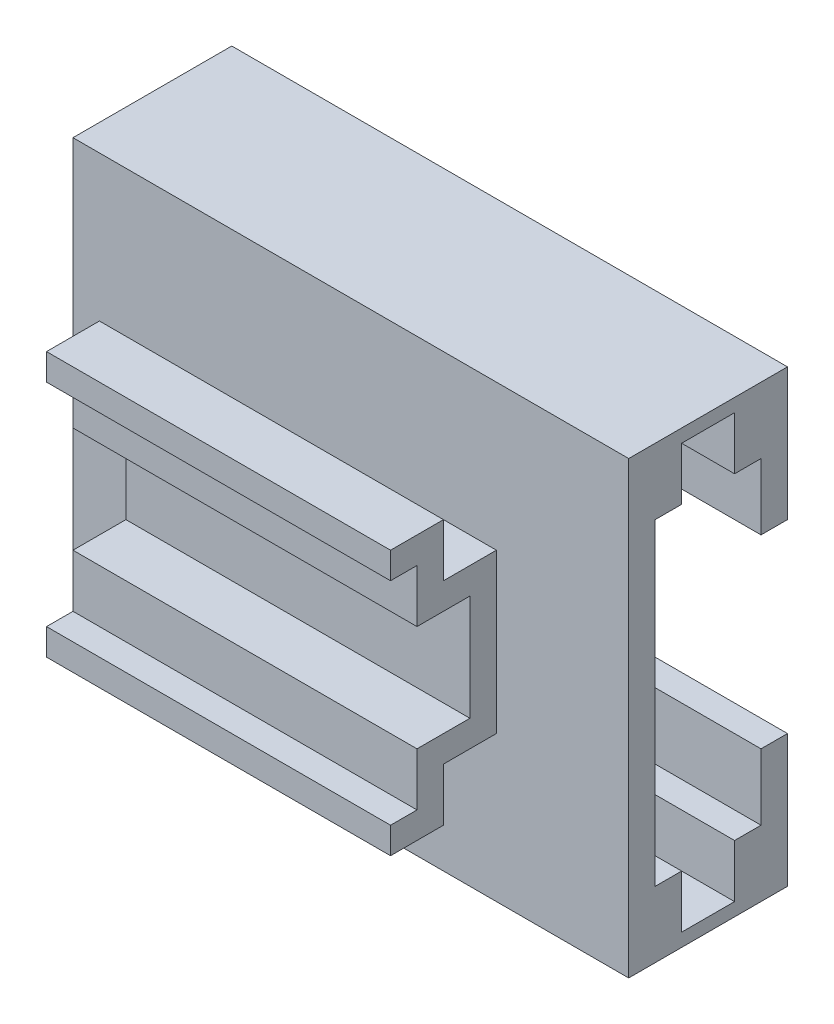
SolidWorks part; units mm, degrees
note: The reader was unsure of these and kept them because the rebuilt part matched: shared geometry of "Esquisse1<3>", "Esquisse1<4>", "Esquisse1<6>".
ref_plane "Plan de face" through (0, 0, 0) normal (0, 0, 1) x (1, 0, 0)
ref_plane "Plan de dessus" through (0, 0, 0) normal (0, 1, 0) x (1, 0, 0)
ref_plane "Plan de droite" through (0, 0, 0) normal (1, 0, 0) x (0, 0, -1)
sketch "Esquisse1" plane through (0, 0, 0) normal (0, 0, 1) x (1, 0, 0)
  line L0 (-10.5, 6) -> (10.5, 6)
  line L1 (10.5, 8.5) -> (-10.5, 8.5)
  line L2 (10.5, 8.5) -> (10.5, -8.5)
  line L3 (10.5, -8.5) -> (-10.5, -8.5)
  line L4 (-10.5, 8.5) -> (-10.5, -8.5)
  line L5 (10.5, 8.5) -> (-10.5, -8.5) construction
  line L6 (10.5, -8.5) -> (-10.5, 8.5) construction
  line L7 (-10.5, -6) -> (10.5, -6)
  line L8 (-9, -8) -> (10.5, -8)
  line L9 (-9, -8) -> (-9, -6)
  line L10 (-12.4007, 0) -> (12.7242, 0) construction
  line L12 (-9, 8) -> (10.5, 8)
  line L13 (10.5, 3.5) -> (-1, 3.5)
  line L14 (-1, 3.5) -> (-1, -3.5)
  line L15 (10.5, -3.5) -> (-1, -3.5)
  line L16 (-9, 8) -> (-9, 6)
  point P0 (0, 0)
  dimension "D1" = 17
  dimension "D2" = 21
  dimension "D3" = 2.5
  dimension "D4" = 2
  dimension "D5" = 2.5
  dimension "D6" = 1.5
  dimension "D7" = 2
  dimension "D8" = 3.5
  dimension "D9" = 1
extrude "Boss.-Extru.1" add sketch "Esquisse1" along normal blind 1 contours L4 L3 L2 L1
extrude "Boss.-Extru.2" add sketch "Esquisse1<3>" against normal blind 1 from offset 4 separate body contours L15 L2 L13 L14 offset against normal yes
sketch "Esquisse1<3>" plane through (0, 0, 0) normal (0, 0, 1) x (1, 0, 0) same geometry as "Esquisse1"
extrude "Boss.-Extru.3" add sketch "Esquisse1<4>" against normal blind 4
sketch "Esquisse1<4>" plane through (0, 0, 0) normal (0, 0, 1) x (1, 0, 0) same geometry as "Esquisse1"
extrude "Enlèv. mat.-Extru.1" cut sketch "Esquisse1<6>" against normal blind 2 from offset 1 contours L9 L8 L2 L7 | L12 L16 L0 L2 offset against normal yes
sketch "Esquisse1<6>" plane through (0, 0, 0) normal (0, 0, 1) x (1, 0, 0) same geometry as "Esquisse1"
sketch "Esquisse2" plane through (-10.5, 0, 0) normal (-1, 0, 0) x (0, 0, 1)
  line L0 (-1.889, 0) -> (9.1913, 0) construction
  line L1 (1, 3) -> (3, 3)
  line L2 (1, 8.5) -> (1, -8.5) construction
  line L3 (3, 3) -> (3, 5)
  line L4 (3, 5) -> (5, 5)
  line L5 (5, 5) -> (5, 4)
  line L6 (3, -3) -> (3, -5)
  line L7 (1, -3) -> (3, -3)
  line L8 (3, -5) -> (5, -5)
  line L9 (1, 3) -> (1, -3)
  line L10 (2, 2) -> (2, -2)
  line L11 (2, -2) -> (4, -2)
  line L12 (4, -2) -> (4, -4)
  line L13 (4, -4) -> (4, -4)
  line L15 (4, 4) -> (4, 4)
  line L16 (4, 2) -> (4, 4)
  line L17 (2, 2) -> (4, 2)
  line L18 (4, -4) -> (5, -4)
  line L19 (4, 4) -> (5, 4)
  line L20 (5, -4) -> (5, -5)
  line L22 (5, 5) -> (5, -5) construction
  line L23 (4, 4) -> (4, -4) construction
  point P11 (5, 0)
  line M8 (1, -8.5) -> (1, 8.5)
  dimension "D1" = 2
  dimension "D2" = 2
  dimension "D3" = 5
  dimension "D4" = 3
  dimension "D5" = 1
extrude "Boss.-Extru.4" add sketch "Esquisse2" against normal blind 13 from offset 3 contours L20 L18 L12 L11 L10 L17 L16 L19 L5 L4 L3 L1 L7 L6 L8 M8
